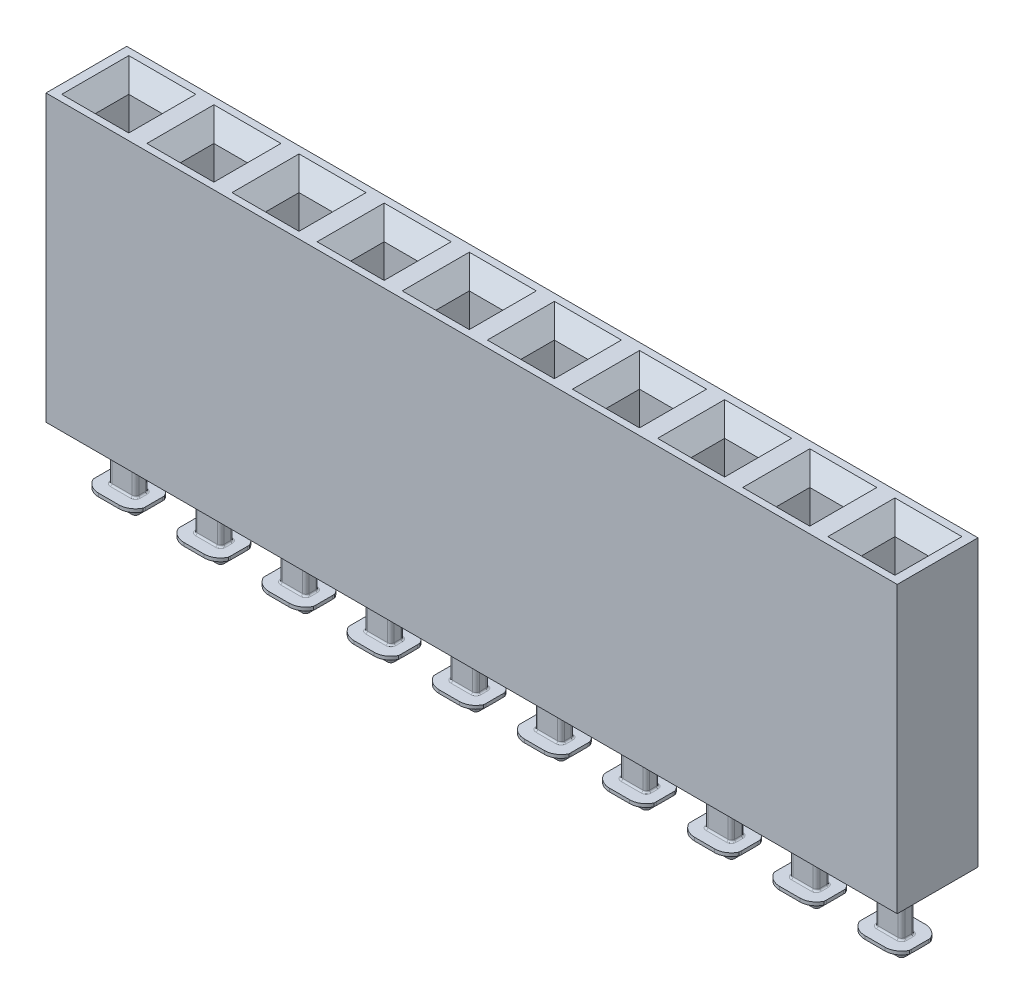
SolidWorks part; units mm, degrees
other "pin"
other "corpo" parameters "D1"=2.41, "D2"=2.41, "D3"=6.4991, "D4"=4.5449
ref_plane "Front Plane" through (0, 0, 0) normal (0, 0, 1) x (1, 0, 0)
ref_plane "Top Plane" through (0, 0, 0) normal (0, 1, 0) x (1, 0, 0)
ref_plane "Right Plane" through (0, 0, 0) normal (1, 0, 0) x (0, 0, -1)
sketch "Sketch1" plane through (0, 0, 0) normal (0, 1, 0) x (1, 0, 0)
  line L1 (-1.27, -1.2) -> (24.13, -1.2)
  line L2 (-1.27, -1.2) -> (-1.27, 1.21)
  line L3 (-1.27, 1.21) -> (24.13, 1.21)
  line L4 (24.13, -1.2) -> (24.13, 1.21)
  dimension "D1" = 2.41
  dimension "D2" = 25.4
  dimension "D3" = 1.21
  dimension "D4" = 1.27
extrude "Boss-Extrude1" add sketch "Sketch1" along normal blind 8.51
sketch "Sketch2" plane through (0, 8.51, 0) normal (0, 1, 0) x (1, 0, 0)
  line L1 (-0.5, 0.5) -> (0.5, 0.5)
  line L2 (-0.5, 0.5) -> (-0.5, -0.5)
  line L3 (-0.5, -0.5) -> (0.5, -0.5)
  line L4 (0.5, 0.5) -> (0.5, -0.5)
  line L5 (-0.5, 0.5) -> (0.5, -0.5) construction
  line L6 (-0.5, -0.5) -> (0.5, 0.5) construction
  point P0 (0, 0)
  dimension "D1" = 1
extrude "Cut-Extrude1" cut sketch "Sketch2" against normal blind 5
chamfer "Chamfer1" distance 0.5 angle 45 4 edges at (0.5, 8.51, 0) (0, 8.51, 0.5) (-0.5, 8.51, 0) (0, 8.51, -0.5)
pattern_linear "LPattern1" count 10 spacing 2.54 along (1, 0, 0) of "Cut-Extrude1", "Chamfer1"
sketch "Sketch3" plane through (0, 0, 0) normal (0, -1, 0) x (1, 0, 0)
  line L1 (-0.4, 0.2) -> (0.4, 0.2)
  line L2 (-0.4, 0.2) -> (-0.4, -0.2)
  line L3 (-0.4, -0.2) -> (0.4, -0.2)
  line L4 (0.4, 0.2) -> (0.4, -0.2)
  line L5 (-0.4, 0.2) -> (0.4, -0.2) construction
  line L6 (-0.4, -0.2) -> (0.4, 0.2) construction
  circle A0 centre (0, 0) radius 0.5 construction
  point P0 (0, 0)
  dimension "D3" = 1
  dimension "D1" = 0.4
  dimension "D2" = 0.8
extrude "Boss-Extrude2" add sketch "Sketch3" along normal blind 2.1 and the other way blind 3.51 separate body
sketch "Sketch6" plane through (0, 3.51, 0) normal (0, 1, 0) x (1, 0, 0)
  line L0 (-0.4, -0.2) -> (0.4, 0.2) construction
  circle A0 centre (0, 0) radius 0.4472
extrude "Cut-Extrude2" cut sketch "Sketch6" against normal through all
pattern_linear "LPattern4" count 10 spacing 2.54 along (1, 0, 0) of "Cut-Extrude2"
sketch "Sketch7" plane through (0, 3.51, 0) normal (0, 1, 0) x (1, 0, 0)
  line L4 (0.5, -0.5) -> (0.5, 0.5)
  line L5 (0.5, 0.5) -> (-0.5, 0.5)
  line L6 (-0.5, 0.5) -> (-0.5, -0.5)
  line L7 (-0.5, -0.5) -> (0.5, -0.5)
  line L8 (0.5, -0.5) -> (0.5, 0.5)
  line L9 (0.5, 0.5) -> (-0.5, 0.5)
  line L10 (-0.5, 0.5) -> (-0.5, -0.5)
  line L11 (-0.5, -0.5) -> (0.5, -0.5)
  dimension "D1" = 0
extrude "Boss-Extrude4" add sketch "Sketch7" along normal blind 0.5
fillet "Fillet3" radius 0.2 4 edges at (0.5, 3.76, -0.5) (-0.5, 3.76, -0.5) (-0.5, 3.76, 0.5) (0.5, 3.76, 0.5)
fillet "Fillet1" radius 0.1 4 edges at (0.4, 0.705, -0.2) (-0.4, 0.705, -0.2) (0.4, 0.705, 0.2) (-0.4, 0.705, 0.2)
sketch "Sketch4" plane through (0, -2.1, 0) normal (0, -1, 0) x (1, 0, 0)
  line L0 (0, -0.25) -> (0, 0.25) construction
  line L1 (-0.75, -0.25) -> (-0.75, 0.25)
  line L2 (0.75, -0.25) -> (0.75, 0.25)
  arc A0 (-0.75, -0.25) -> (0.75, -0.25) centre (0, -0.25) ccw
  arc A1 (0.75, 0.25) -> (-0.75, 0.25) centre (0, 0.25) ccw
  point P2 (0, 0)
  dimension "D1" = 0.5
  dimension "D2" = 1.5
extrude "Boss-Extrude3" add sketch "Sketch4" against normal blind 0.1 from offset 0.35 offset against normal yes
fillet "Fillet2" radius 0.4 6 edges at (0.3707, -1.75, 0.1707) (0.3707, -1.75, -0.1707) (0, -1.75, -0.2) (-0.3707, -1.75, -0.1707) (-0.3707, -1.75, 0.1707) (0, -1.75, 0.2)
fillet "Fillet4" radius 0.05 32 edges at (0.3707, 3.51, 0.1707) (0.4, 3.51, 0) (0.3707, 3.51, -0.1707) (0, 3.51, -0.2) (-0.3707, 3.51, -0.1707) (-0.4, 3.51, 0) (-0.3707, 3.51, 0.1707) (0, 3.51, 0.2) (-0.3707, -1.65, 0.1707) (-0.4, -1.65, 0) (-0.3707, -1.65, -0.1707) (0, -1.65, -0.2) (0.3707, -1.65, -0.1707) (0.4, -1.65, 0) (0.3707, -1.65, 0.1707) (-0.4414, 4.01, 0.4414) (-0.5, 4.01, 0) (-0.4414, 4.01, -0.4414) (0, 4.01, -0.5) (0.4414, 4.01, -0.4414) (0.5, 4.01, 0) (0.4414, 4.01, 0.4414) (-0.4414, 3.51, 0.4414) (-0.5, 3.51, 0) (-0.4414, 3.51, -0.4414) (0, 3.51, -0.5) (0.4414, 3.51, -0.4414) (0.5, 3.51, 0) (0.4414, 3.51, 0.4414) (0, -1.65, 0.2) (0, 4.01, 0.5) (0, 3.51, 0.5)
sketch "Sketch8" plane through (0, -2.1, 0) normal (0, -1, 0) x (1, 0, 0)
  line L3 (0.3, -0.5969) -> (-0.3, -0.5969)
  line L4 (0.3, -0.5969) -> (-0.3, -0.5969)
  line L5 (-0.3, 0.5969) -> (0.3, 0.5969)
  line L6 (-0.3, 0.5969) -> (0.3, 0.5969)
  arc A7 (-0.747, -0.3169) -> (-0.3, -0.5969) centre (-0.3, -0.1) ccw
  arc A8 (-0.747, -0.3169) -> (0.747, -0.3169) centre (0, -0.25) ccw
  arc A9 (0.3, -0.5969) -> (0.747, -0.3169) centre (0.3, -0.1) ccw
  arc A10 (-0.747, -0.3169) -> (-0.3, -0.5969) centre (-0.3, -0.1) ccw
  arc A11 (-0.747, -0.3169) -> (0.747, -0.3169) centre (0, -0.25) ccw
  arc A12 (0.3, -0.5969) -> (0.747, -0.3169) centre (0.3, -0.1) ccw
  arc A13 (0.747, 0.3169) -> (-0.747, 0.3169) centre (0, 0.25) ccw
  arc A14 (-0.3, 0.5969) -> (-0.747, 0.3169) centre (-0.3, 0.1) ccw
  arc A15 (0.747, 0.3169) -> (0.3, 0.5969) centre (0.3, 0.1) ccw
  arc A16 (0.747, 0.3169) -> (-0.747, 0.3169) centre (0, 0.25) ccw
  arc A17 (-0.3, 0.5969) -> (-0.747, 0.3169) centre (-0.3, 0.1) ccw
  arc A18 (0.747, 0.3169) -> (0.3, 0.5969) centre (0.3, 0.1) ccw
  dimension "D1" = 0
  dimension "D2" = 0
extrude "Cut-Extrude3" cut sketch "Sketch8" against normal up to surface (0.45 mm away) up to face at (0, -1.65, 0)
pattern_linear "LPattern5" count 10 spacing 2.54 along (1, 0, 0) of bodies 122 105
equation "\"pin\"= 10"
equation "\"D2@Sketch1\"=\"pin\"*2.54"
equation "\"D1@LPattern1\"=\"pin\""
equation "\"D1@LPattern4\"=\"pin\""
equation "\"D1@LPattern5\"=\"pin\""
